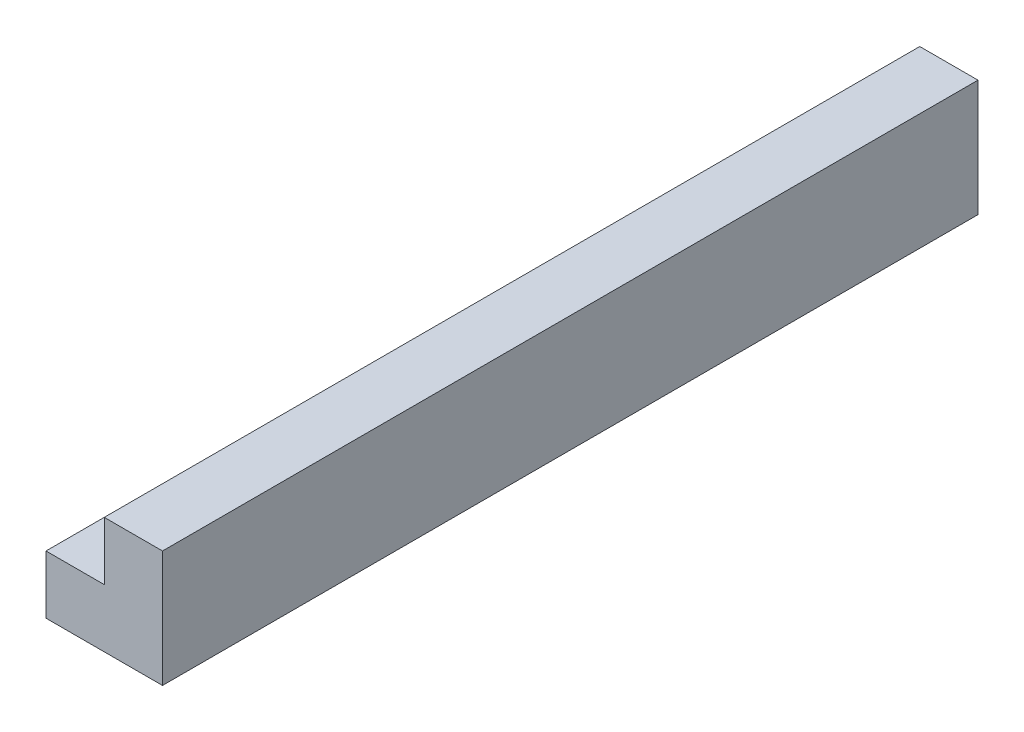
SolidWorks part; units mm, degrees
ref_plane "Plan de face" through (0, 0, 0) normal (0, 0, 1) x (1, 0, 0)
ref_plane "Plan de dessus" through (0, 0, 0) normal (0, 1, 0) x (1, 0, 0)
ref_plane "Plan de droite" through (0, 0, 0) normal (1, 0, 0) x (0, 0, -1)
sketch "Esquisse1" plane through (0, 0, 0) normal (0, 0, 1) x (1, 0, 0)
  line L0 (0, 0) -> (20, 0)
  line L1 (0, 0) -> (20, 0) construction
  line L2 (0, 0) -> (0, 20) construction
  line L3 (0, 20) -> (20, 20) construction
  line L4 (20, 0) -> (20, 20) construction
  line L5 (20, 0) -> (20, 20)
  line L6 (20, 20) -> (10, 20)
  line L7 (10, 20) -> (10, 10)
  line L8 (10, 10) -> (0, 10)
  line L9 (0, 10) -> (0, 0)
  dimension "D1" = 20
  dimension "D2" = 20
extrude "Boss.-Extru.1" add sketch "Esquisse1" along normal blind 140
equation "\"Largeur\"= 20"
equation "\"Longueur\"= 140"
equation "\"Hauteur\"= 20"
equation "\"D1@Esquisse1\"=\"Largeur\""
equation "\"D2@Esquisse1\"=\"Hauteur\""
equation "\"D1@Boss.-Extru.1\"=\"Longueur\""
